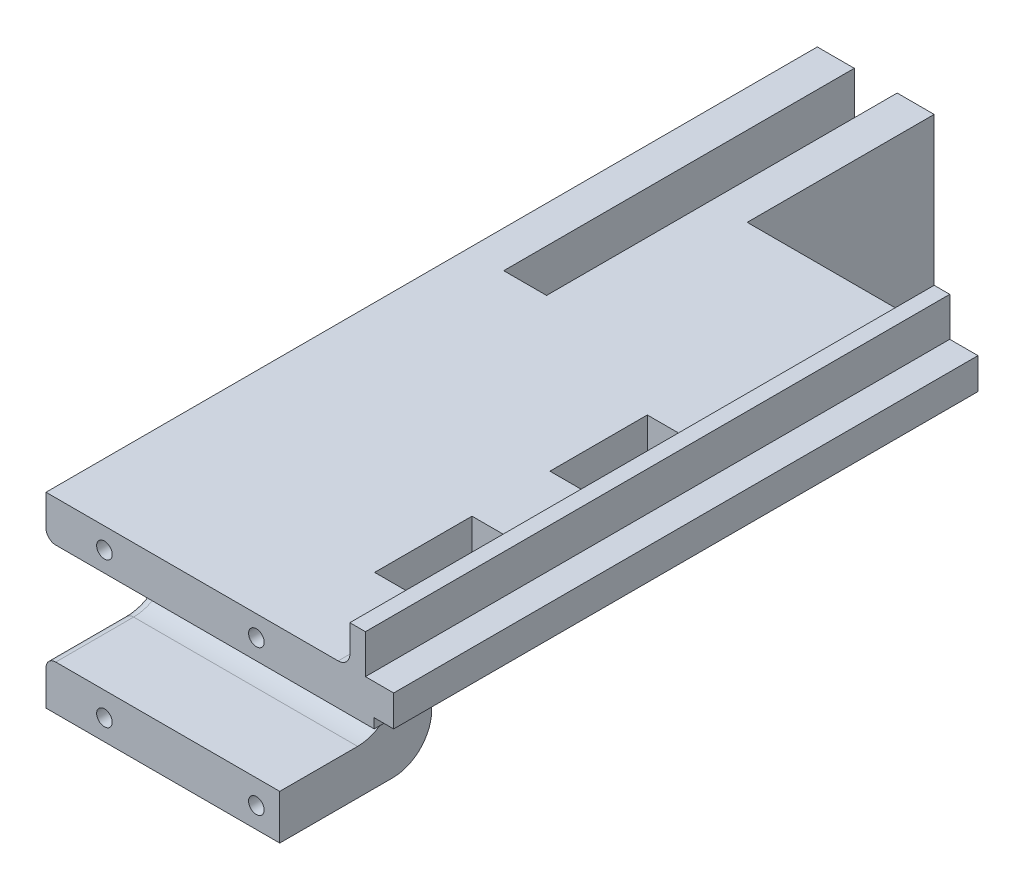
SolidWorks part; units mm, degrees
ref_plane "Alzado" through (0, 0, 0) normal (0, 0, 1) x (1, 0, 0)
ref_plane "Planta" through (0, 0, 0) normal (0, 1, 0) x (1, 0, 0)
ref_plane "Vista lateral" through (0, 0, 0) normal (1, 0, 0) x (0, 0, -1)
sketch "Croquis1" plane through (0, 0, 0) normal (0, 0, 1) x (1, 0, 0)
  line L1 (-66.2162, 31.0113) -> (-6.2162, 31.0113)
  line L2 (-66.2162, 31.0113) -> (-66.2162, -16.9887)
  line L3 (-66.2162, -16.9887) -> (-6.2162, -16.9887)
  line L4 (-6.2162, 31.0113) -> (-6.2162, -16.9887)
  dimension "D1" = 48
  dimension "D2" = 60
extrude "Saliente-Extruir1" add sketch "Croquis1" along normal blind 6
sketch "Croquis4" plane through (0, 0, 6) normal (0, 0, 1) x (1, 0, 0)
  line L0 (-66.2162, 31.0113) -> (-66.2162, 19.5113)
  line L1 (-66.2162, 31.0113) -> (-66.2162, -16.9887) construction
  line L3 (-66.2162, -5.4887) -> (-66.2162, -16.9887)
  line L4 (-66.2162, 31.0113) -> (-6.2162, 31.0113)
  line L6 (-6.2162, 31.0113) -> (-6.2162, 19.5113)
  line L7 (-6.2162, -16.9887) -> (-6.2162, 31.0113) construction
  line L8 (-6.2162, 19.5113) -> (-66.2162, 19.5113)
  line L9 (-66.2162, -5.4887) -> (-6.2162, -5.4887)
  line L10 (-6.2162, -5.4887) -> (-6.2162, -16.9887)
  line L11 (-6.2162, -16.9887) -> (-66.2162, -16.9887)
  dimension "D1" = 25
extrude "Saliente-Extruir3" add sketch "Croquis4" along normal blind 30
sketch "Croquis3" plane through (0, 0, 6) normal (0, 0, 1) x (1, 0, 0)
  circle A0 centre (-51.2162, 25.6613) radius 2.125
  circle A1 centre (-12.2162, 25.6613) radius 2.125
  circle A2 centre (-12.2162, -11.6387) radius 2.125
  circle A3 centre (-51.2162, -11.6387) radius 2.125
  dimension "D7" = 4.25
  dimension "D9" = 4.25
  dimension "D10" = 4.25
  dimension "D2" = 4.25
  dimension "D3" = 37.3
  dimension "D4" = 39
sketch "Croquis5" plane through (0, 0, 36) normal (0, 0, 1) x (1, 0, 0)
  circle A0 centre (-51.2162, 25.6613) radius 2
  circle A1 centre (-12.2162, 25.6613) radius 2
  circle A2 centre (-12.2162, -11.6387) radius 2
  circle A3 centre (-51.2162, -11.6387) radius 2
  dimension "D1" = 4
  dimension "D2" = 4
  dimension "D3" = 4
  dimension "D4" = 4
extrude "Cortar-Extruir3" cut sketch "Croquis5" against normal blind 16
sketch "Croquis6" plane through (0, 0, 0) normal (0, 0, -1) x (-1, 0, 0)
  line L0 (66.2162, -16.9887) -> (6.2162, -16.9887) construction
  line L1 (66.2162, 31.0113) -> (36.2162, 31.0113)
  line L2 (66.2162, 31.0113) -> (66.2162, -16.9887)
  line L3 (66.2162, -16.9887) -> (36.2162, -16.9887)
  line L4 (36.2162, 31.0113) -> (36.2162, -16.9887)
  dimension "D1" = 30
extrude "Saliente-Extruir4" add sketch "Croquis6" along normal blind 162
sketch "Croquis7" plane through (0, 0, -162) normal (0, 0, -1) x (-1, 0, 0)
  circle A0 centre (51.2162, 7.0113) radius 2
  dimension "D1" = 4
extrude "Cortar-Extruir4" cut sketch "Croquis7" against normal blind 16
sketch "Croquis8" plane through (0, 0, -162) normal (0, 0, -1) x (-1, 0, 0)
  line L0 (41.2162, 12.0113) -> (41.2162, 9.5131)
  line L10 (36.2162, 12.0113) -> (41.2162, 12.0113)
  line L11 (36.2162, 12.0113) -> (36.2162, 2.0113)
  line L12 (36.2162, 2.0113) -> (41.2162, 2.0113)
  line L21 (41.2162, 9.5131) -> (44.2162, 9.5131)
  line L23 (41.2162, 4.5131) -> (44.2162, 4.5131)
  line L24 (44.2162, 9.5131) -> (44.2162, 4.5131)
  line L25 (41.2162, 2.0113) -> (41.2162, 4.5131)
  dimension "D1" = 5
  dimension "D2" = 3
  dimension "D3" = 5
sketch "Croquis11" plane through (-36.2162, 0, 0) normal (1, 0, 0) x (0, 0, -1)
  line L1 (-36, 19.5113) -> (-36, 31.0113) construction
  line L4 (-36, 19.5113) -> (-36, 31.0113)
  line L6 (-36, 19.5113) -> (114, 19.5113)
  line L7 (114, 19.5113) -> (114, 31.0113)
  line L8 (162, 31.0113) -> (0, 31.0113) construction
  line L9 (162, 31.0113) -> (0, 31.0113) construction
  line L10 (-36, 31.0113) -> (114, 31.0113)
  dimension "D1" = 150
extrude "Saliente-Extruir6" add sketch "Croquis11" along normal blind 59.25
sketch "Croquis12" plane through (0, 31.0113, 0) normal (0, 1, 0) x (1, 0, 0)
  line L0 (23.0338, -36) -> (-66.2162, -36) construction
  line L1 (15.7838, -36) -> (11.7838, -36)
  line L2 (-66.2162, -36) -> (-66.2162, 162) construction
  line L3 (-66.2162, -36) -> (-66.2162, 162) construction
  line L4 (15.7838, -36) -> (15.7838, 114)
  line L5 (15.7838, 114) -> (11.7838, 114)
  line L6 (23.0338, 114) -> (-36.2162, 114) construction
  line L7 (11.7838, 114) -> (11.7838, -36)
  dimension "D1" = 82
  dimension "D2" = 150
  dimension "D3" = 4
extrude "Saliente-Extruir7" add sketch "Croquis12" along normal blind 10
sketch "Croquis14" plane through (0, 0, -114) normal (0, 0, -1) x (-1, 0, 0)
  line L0 (-23.0338, 23.0113) -> (-18.0338, 23.0113)
  line L1 (-18.0338, 23.0113) -> (-18.0338, 19.5113)
  line L2 (-23.0338, 23.0113) -> (-23.0338, 19.5113)
  line L3 (-23.0338, 19.5113) -> (-18.0338, 19.5113)
  line L4 (36.2162, 19.5113) -> (36.2162, 31.0113)
  line L5 (36.2162, 31.0113) -> (-11.7838, 31.0113)
  line L6 (-23.0338, 31.0113) -> (-23.0338, 19.5113)
  line L7 (-23.0338, 19.5113) -> (36.2162, 19.5113)
  line L8 (36.2162, 19.5113) -> (36.2162, 31.0113) construction
  line L9 (36.2162, 31.0113) -> (-11.7838, 31.0113) construction
  line L10 (-23.0338, 31.0113) -> (-23.0338, 19.5113) construction
  line L11 (-23.0338, 19.5113) -> (36.2162, 19.5113) construction
  line L20 (-11.7838, 31.0113) -> (-11.7838, 41.0113)
  line L22 (-11.7838, 41.0113) -> (-15.7838, 41.0113)
  line L24 (-15.7838, 41.0113) -> (-15.7838, 31.0113)
  line L26 (-15.7838, 31.0113) -> (-23.0338, 31.0113)
  line L27 (-15.7838, 31.0113) -> (-23.0338, 31.0113) construction
  dimension "D2" = 5
  dimension "D3" = 8
  dimension "D1" = 0
extrude "Cortar-Extruir6" cut sketch "Croquis14" against normal through all both and the other way through all
sketch "Croquis15" plane through (0, 0, -162) normal (0, 0, -1) x (-1, 0, 0)
  line L0 (51.2162, 45.0729) -> (51.2162, 16.9496) construction
  line L1 (56.7162, 20.0113) -> (45.7162, 20.0113)
  line L2 (45.7162, 20.0113) -> (45.7162, 31.0113)
  line L3 (56.7162, 20.0113) -> (56.7162, 31.0113)
  line L4 (66.2162, -16.9887) -> (66.2162, 31.0113)
  line L5 (66.2162, 31.0113) -> (36.2162, 31.0113)
  line L6 (36.2162, 31.0113) -> (36.2162, -16.9887)
  line L7 (36.2162, -16.9887) -> (66.2162, -16.9887)
  line L8 (66.2162, -16.9887) -> (66.2162, 31.0113) construction
  line L9 (66.2162, 31.0113) -> (36.2162, 31.0113) construction
  line L10 (56.7162, 31.0113) -> (45.7162, 31.0113)
  point P6 (51.2162, 31.0113)
  point P10 (51.2162, 20.0113)
  dimension "D2" = 11
  dimension "D3" = 11
  dimension "D1" = 0
extrude "Cortar-Extruir7" cut sketch "Croquis15" against normal blind 90 and the other way through all
sketch "Croquis16" plane through (-66.2162, 0, 0) normal (-1, 0, 0) x (0, 0, 1)
  line L0 (6, 19.5113) -> (6, 20.5113)
  line L1 (6, 20.5113) -> (36, 20.5113)
  line L2 (36, 31.0113) -> (36, 19.5113) construction
  line L3 (6, 19.5113) -> (36, 19.5113)
  line L4 (36, 19.5113) -> (36, 20.5113)
  dimension "D1" = 1
extrude "Cortar-Extruir10" cut sketch "Croquis16" against normal through all contours L1 L4 L3 L0
fillet "Redondeo1" radius 10 2 edges at (-36.2162, -5.4887, 6) (-24.0912, 20.5113, 6)
sketch "Croquis20" plane through (0, 0, 0) normal (0, 0, -1) x (-1, 0, 0)
  line L1 (6.2162, 19.5113) -> (36.2162, 19.5113)
  line L2 (6.2162, 19.5113) -> (6.2162, -16.9887)
  line L3 (6.2162, -16.9887) -> (36.2162, -16.9887)
  line L4 (36.2162, 19.5113) -> (36.2162, -16.9887)
extrude "Saliente-Extruir8" add sketch "Croquis20" along normal blind 50
sketch "Croquis21" plane through (0, 19.5113, 0) normal (0, -1, 0) x (1, 0, 0)
  line L1 (2.7838, 11.6411) -> (-6.2162, 11.6411)
  line L2 (2.7838, 11.6411) -> (2.7838, -13.3589)
  line L3 (2.7838, -13.3589) -> (-6.2162, -13.3589)
  line L4 (-6.2162, 11.6411) -> (-6.2162, -13.3589)
  line L5 (18.0338, 11.6411) -> (-6.2162, 11.6411) construction
  line L6 (-6.2162, 36) -> (-6.2162, -50) construction
  line L12 (-1.7162, 23.4456) -> (-1.7162, -75.1671) construction
  line L13 (2.7838, -33.3589) -> (2.7838, -58.3589)
  line L14 (2.7838, -33.3589) -> (-6.2162, -33.3589)
  line L15 (-6.2162, -33.3589) -> (-6.2162, -58.3589)
  line L16 (2.7838, -58.3589) -> (-6.2162, -58.3589)
  point P10 (-1.7162, -13.3589)
  dimension "D1" = 9
  dimension "D2" = 25
  dimension "D3" = 2
  dimension "D4" = 20
extrude "Cortar-Extruir11" cut sketch "Croquis21" against normal blind 40
sketch "Croquis22" plane through (0, 0, -50) normal (0, 0, -1) x (-1, 0, 0)
  line L1 (36.2162, 19.5113) -> (6.2162, 19.5113)
  line L2 (36.2162, 19.5113) -> (36.2162, -16.9887)
  line L3 (36.2162, -16.9887) -> (6.2162, -16.9887)
  line L4 (6.2162, 19.5113) -> (6.2162, -16.9887)
extrude "Cortar-Extruir13" cut sketch "Croquis22" against normal blind 47
fillet "Redondeo3" radius 10 1 edges at (-21.2162, -16.9887, -3)
sketch "Croquis23" plane through (0, 0, 36) normal (0, 0, 1) x (1, 0, 0)
  circle A0 centre (-12.2162, -11.6387) radius 2 construction
  circle A1 centre (-51.2162, -11.6387) radius 2 construction
  circle A2 centre (-12.2162, 25.6613) radius 2 construction
  circle A3 centre (-51.2162, 25.6613) radius 2 construction
  circle A4 centre (-12.2162, -11.6387) radius 2
  circle A5 centre (-51.2162, -11.6387) radius 2
  circle A6 centre (-12.2162, 25.6613) radius 2
  circle A7 centre (-51.2162, 25.6613) radius 2
extrude "Cortar-Extruir14" cut sketch "Croquis23" against normal blind 16
fillet "Redondeo4" radius 3 1 edges at (11.7838, 31.0113, -39)
sketch "Croquis24" plane through (0, 0, -162) normal (0, 0, -1) x (-1, 0, 0)
  line L0 (36.2162, -16.9887) -> (66.2162, -16.9887) construction
  line L1 (36.2162, -16.9887) -> (66.2162, -16.9887) construction
  line L2 (51.2162, 1.6971) -> (51.2162, -35.6746) construction
  line L3 (48.7162, -16.9887) -> (48.7162, -12.9887)
  line L4 (48.7162, -12.9887) -> (44.2162, -12.9887)
  line L5 (44.2162, -12.9887) -> (44.2162, -8.9887)
  line L6 (44.2162, -8.9887) -> (58.2162, -8.9887)
  line L7 (48.7162, -16.9887) -> (53.7162, -16.9887)
  line L8 (58.2162, -12.9887) -> (58.2162, -8.9887)
  line L9 (53.7162, -12.9887) -> (58.2162, -12.9887)
  line L10 (53.7162, -16.9887) -> (53.7162, -12.9887)
  point P5 (51.2162, -16.9887)
  point P12 (51.2162, -16.9887)
  point P13 (51.2162, -8.9887)
  dimension "D1" = 4
  dimension "D2" = 4
  dimension "D3" = 7
  dimension "D4" = 2.5
extrude "Cortar-Extruir15" cut sketch "Croquis24" against normal blind 170
fillet "Redondeo5" radius 6 1 edges at (-36.2162, 19.5113, -58.5)
fillet "Redondeo6" radius 2.5 5 edges at (-66.2162, 20.5113, 26) (-66.2162, 17.5823, 8.9289) (-66.2162, 7.5113, 6) (-66.2162, -2.5598, 8.9289) (-66.2162, -5.4887, 26)
